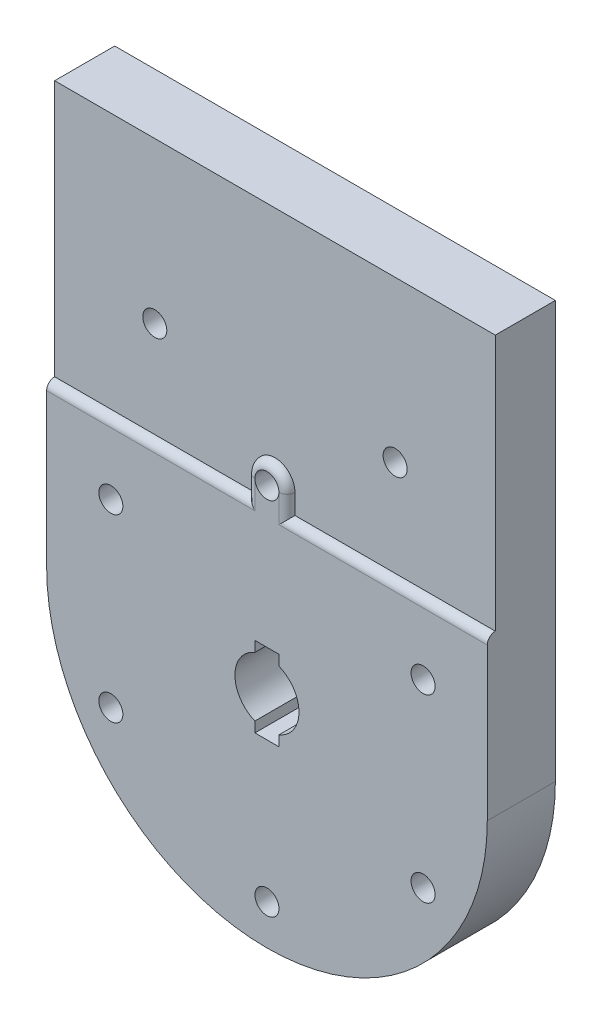
SolidWorks part; units mm, degrees
ref_plane "Plan de face" through (0, 0, 0) normal (0, 0, 1) x (1, 0, 0)
ref_plane "Plan de dessus" through (0, 0, 0) normal (0, 1, 0) x (1, 0, 0)
ref_plane "Plan de droite" through (0, 0, 0) normal (1, 0, 0) x (0, 0, -1)
sketch "Esquisse1" plane through (0, 0, 0) normal (0, 0, 1) x (1, 0, 0)
  line L0 (-50, 52) -> (50, 52)
  line L1 (-50, 52) -> (-50, -48.5481)
  line L2 (50, 52) -> (50, -48.5481)
  line L3 (-50, -48.5481) -> (50, -48.5481)
  line L10 (-1.5, 5) -> (1.5, 5)
  line L11 (-1.5, 5) -> (-1.5, -5)
  line L12 (-1.5, -5) -> (1.5, -5)
  line L13 (1.5, 5) -> (1.5, -5)
  circle A1 centre (0, 0) radius 4
  dimension "D1" = 52
  dimension "D3" = 3
  dimension "D2" = 10
  dimension "D4" = 1.5
  dimension "D5" = 5
extrude "Boss.-Extru.1" add sketch "Esquisse1" along normal blind 8.5
sketch "Esquisse2" plane through (0, 0, 8.5) normal (0, 0, 1) x (1, 0, 0)
  line L0 (-27.5, 0) -> (27.5, 0)
  line L1 (-27.5, 0) -> (-27.5, 55)
  line L2 (27.5, 0) -> (27.5, 55)
  line L3 (-27.5, 55) -> (27.5, 55)
  line L4 (-50, 52) -> (50, 52) construction
  circle A0 centre (0, 22.5) radius 1.5
  circle A1 centre (19.4856, 11.25) radius 1.5
  circle A2 centre (19.4856, -11.25) radius 1.5
  circle A3 centre (0, -22.5) radius 1.5
  circle A4 centre (-19.4856, -11.25) radius 1.5
  circle A5 centre (-19.4856, 11.25) radius 1.5
  circle A6 centre (0, 0) radius 27.5
  circle A13 centre (-15, 32) radius 1.5
  circle A14 centre (15, 32) radius 1.5
  point P4 (0, 0)
  point P12 (0, 0)
  point P32 (0, 0)
  point P33 (0, 0)
  dimension "D1" = 22.5
  dimension "D3" = 55
  dimension "D4" = 55
  dimension "D8" = 12.5
  dimension "D9" = 12.5
  dimension "D10" = 20
  dimension "D11" = 20
  dimension "D2" = 6
extrude "Enlèv. mat.-Extru.1" cut sketch "Esquisse2" against normal through all
sketch "Esquisse3" plane through (0, 0, 8.5) normal (0, 0, 1) x (1, 0, 0)
  line L0 (-27.5, 52) -> (27.5, 52)
  line L1 (-27.5, 52) -> (-27.5, 20)
  line L2 (27.5, 52) -> (27.5, 20)
  line L3 (-27.5, 20) -> (27.5, 20)
  line L4 (-2.5, 20) -> (2.5, 20)
  line L5 (-2.5, 20) -> (-2.5, 22.5)
  line L6 (2.5, 20) -> (2.5, 22.5)
  line L7 (-2.5, 22.5) -> (2.5, 22.5)
  circle A0 centre (0, 22.5) radius 2.5
  circle M14 centre (-15, 32) radius 1.5
  circle M15 centre (15, 32) radius 1.5
  line M18 (27.5, 0) -> (27.5, 52)
  line M19 (27.5, 52) -> (-27.5, 52)
  line M20 (-27.5, 52) -> (-27.5, 0)
  dimension "D1" = 32
  dimension "D2" = 5
  dimension "D3" = 2.5
  dimension "D4" = 25
extrude "Enlèv. mat.-Extru.6" cut sketch "Esquisse3" against normal blind 1 contours L5 L7 L6 L3 M18 M19 M20 M15 M14
fillet "Congé4" radius 1 5 edges at (-15, 20, 8.5) (15, 20, 8.5) (2.5, 21.25, 8.5) (-2.5, 21.25, 8.5) (0, 25, 8.5)
sketch "Esquisse4" plane through (0, 0, 0) normal (0, 0, -1) x (-1, 0, 0)
  circle A0 centre (0, 22.5) radius 3
  circle A1 centre (19.4856, 11.25) radius 3
  circle A2 centre (19.4856, -11.25) radius 3
  circle A3 centre (0, -22.5) radius 3
  circle A4 centre (-19.4856, -11.25) radius 3
  circle A5 centre (-19.4856, 11.25) radius 3
  point P15 (0, 0)
  dimension "D1" = 6
extrude "Enlèv. mat.-Extru.7" cut sketch "Esquisse4" against normal blind 4
